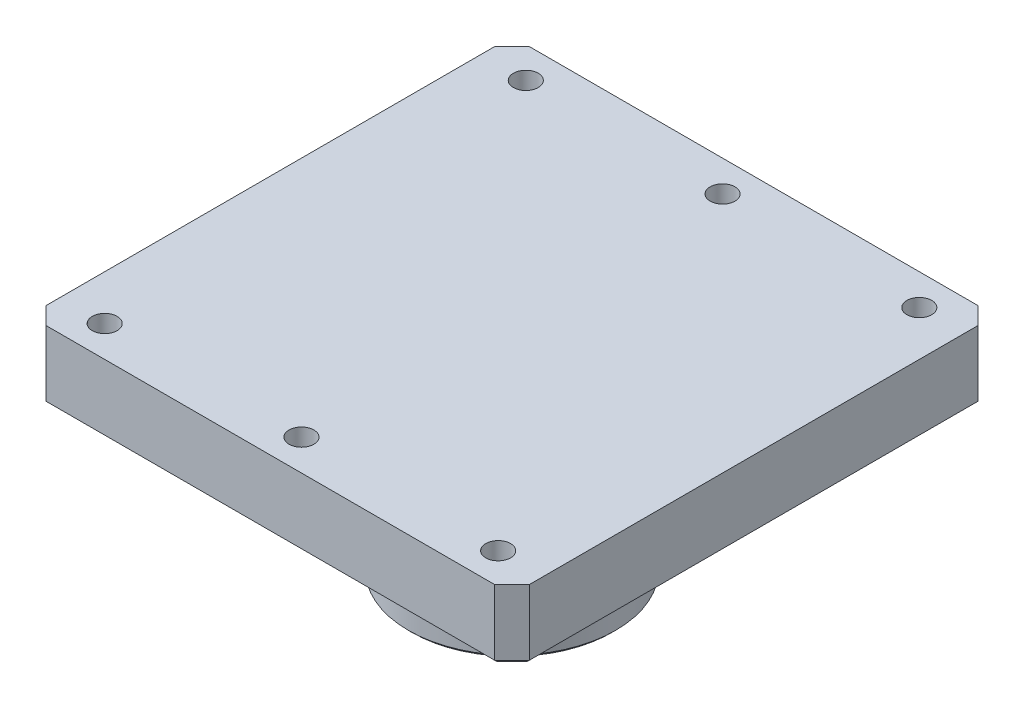
SolidWorks part; units mm, degrees
note: The reader was unsure of these and kept them because the rebuilt part matched: shared geometry of "Sketch1<3>".
ref_plane "Ebene vorne" through (0, 0, 0) normal (0, 0, 1) x (1, 0, 0)
ref_plane "Ebene oben" through (0, 0, 0) normal (0, 1, 0) x (1, 0, 0)
ref_plane "Ebene rechts" through (0, 0, 0) normal (1, 0, 0) x (0, 0, -1)
sketch "Sketch1" plane through (0, 0, 0) normal (0, 1, 0) x (1, 0, 0)
  line L0 (-1.5, 2) -> (1.5, 2)
  line L1 (-35, -35) -> (35, -35)
  line L2 (-35, -35) -> (-35, 35)
  line L3 (-35, 35) -> (35, 35)
  line L4 (35, -35) -> (35, 35)
  line L5 (-35, -35) -> (35, 35) construction
  line L6 (-35, 35) -> (35, -35) construction
  line L7 (0, -2.5) -> (4.1731, -2.5) construction
  circle A0 centre (0, 0) radius 15
  circle A1 centre (0, 0) radius 2.5
  point P0 (0, 0)
  dimension "D2" = 30
  dimension "D3" = 5
  dimension "D1" = 70
  dimension "D4" = 4.5
extrude "Boss-Extrude1" add sketch "Sketch1" along normal blind 10 contours L2 L1 L4 L3
extrude "Boss-Extrude2" add sketch "Sketch1<3>" against normal blind 22.5 contours A0 A1 | L0 A1
sketch "Sketch1<3>" plane through (0, 0, 0) normal (0, 1, 0) x (1, 0, 0) same geometry as "Sketch1"
sketch "Sketch2" plane through (0, 0, 0) normal (0, -1, 0) x (1, 0, 0)
  circle A0 centre (0, 0) radius 25.85
  circle M2 centre (0, 0) radius 15
  dimension "D1" = 51.7
extrude "Cut-Extrude1" cut sketch "Sketch2" against normal blind 1 contours A0 M2
hole_wizard "CBORE for M3 Hex Socket Head Cap Screw1" positions "Sketch3" profile "Sketch4" counterbore size "M3" standard "DIN"
sketch "Sketch3" plane through (0, 0, 0) normal (0, -1, 0) x (-1, 0, 0)
  line L1 (-28.5, 30.5) -> (28.5, 30.5)
  line L2 (-28.5, 30.5) -> (-28.5, -30.5)
  line L3 (-28.5, -30.5) -> (28.5, -30.5)
  line L4 (28.5, 30.5) -> (28.5, -30.5)
  line L5 (-28.5, 30.5) -> (28.5, -30.5) construction
  line L6 (-28.5, -30.5) -> (28.5, 30.5) construction
  line L9 (35, 35) -> (-35, 35) construction
  line L10 (-35, -35) -> (-35, 35) construction
  circle A0 centre (0, 0) radius 15 construction
  point P1 (-28.5, 30.5)
  point P2 (28.5, -30.5)
  point P5 (-28.5, -30.5)
  point P6 (28.5, 30.5)
  point P113 (0, 0)
  point P130 (0, -30.5)
  point P132 (0, 30.5)
  dimension "D1" = 6.5
  dimension "D2" = 4.5
sketch "Sketch4" plane through (28.5, 0, -30.5) normal (1, 0, 0) x (0, 0, -1)
  line L0 (0, 0) -> (0, 10)
  line L1 (0, 10) -> (1.8, 10)
  line L3 (1.8, 10) -> (1.8, 4.4)
  line L4 (1.8, 4.4) -> (3.25, 4.4)
  line L5 (3.25, 4.4) -> (3.25, 0)
  line L7 (3.25, 0) -> (0, 0)
  line L11 (0, -6.35) -> (0, 107.95) construction
  dimension "Thru Hole Dia." = 3.6
  dimension "Thru Hole Depth" = 10
  dimension "C'Bore Dia." = 6.5
  dimension "C'Bore Depth" = 4.4
chamfer "2,5mm Chamfer1" distance 2.5 angle 45 6 edges at (-35, 5, 35) (-35, 0, 0) (-35, 5, -35) (35, 5, 35) (35, 0, 0) (35, 5, -35)
chamfer "0,5mm Chamfer2" distance 0.5 angle 45 18 edges at (33.75, 0, 33.75) (35, 0, 0) (33.75, 0, -33.75) (0, 0, -35) (-33.75, 0, -33.75) (-35, 0, 0) (-33.75, 0, 33.75) (0, 0, 35) (0, 0, -25.85) (0, 0, -33.75) (0, 0, 27.25) (-28.5, 0, -33.75) (28.5, 0, 27.25) (-28.5, 0, 27.25) (28.5, 0, -33.75) (0, -22.5, 2.5) (0, -22.5, -2) (0, -22.5, 15)
